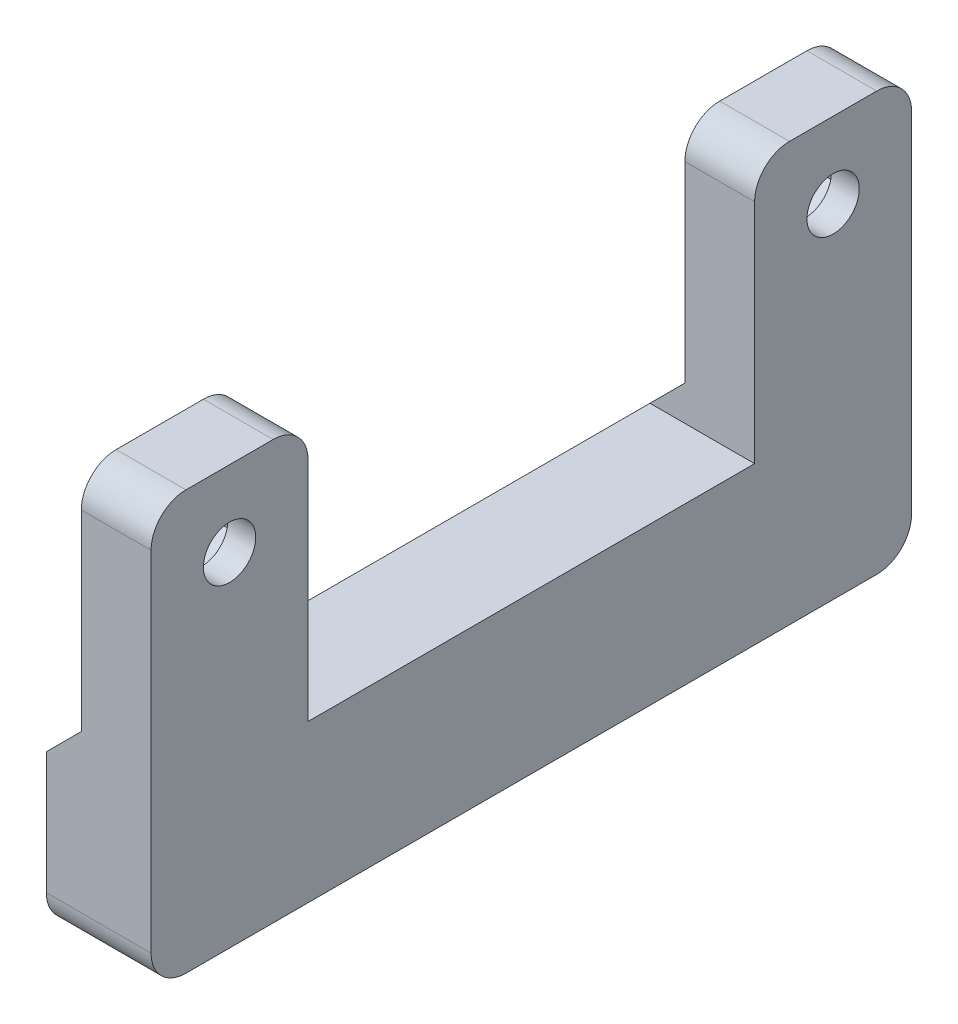
SolidWorks part; units mm, degrees
ref_plane "Спереди" through (0, 0, 0) normal (0, 0, 1) x (1, 0, 0)
ref_plane "Сверху" through (0, 0, 0) normal (0, 1, 0) x (1, 0, 0)
ref_plane "Справа" through (0, 0, 0) normal (1, 0, 0) x (0, 0, -1)
sketch "Эскиз1" plane through (0, 0, 0) normal (1, 0, 0) x (0, 0, -1)
  line L0 (-49.5833, 6.5417) -> (-49.5833, -17.4583)
  line L1 (-49.5833, -17.4583) -> (-5.9833, -17.4583)
  line L2 (-5.9833, -17.4583) -> (-5.9833, 6.5417)
  line L3 (-5.9833, 6.5417) -> (-14.9833, 6.5417)
  line L4 (-14.9833, 6.5417) -> (-14.9833, -8.4583)
  line L5 (-14.9833, -8.4583) -> (-40.5833, -8.4583)
  line L6 (-40.5833, -8.4583) -> (-40.5833, 6.5417)
  line L7 (-40.5833, 6.5417) -> (-49.5833, 6.5417)
  line L8 (-45.0833, 6.5417) -> (-45.0833, -17.4583) construction
  line L9 (-10.4833, 6.5417) -> (-10.4833, -17.4583) construction
  dimension "D1" = 24
  dimension "D2" = 9
  dimension "D3" = 9
  dimension "D4" = 9
  dimension "D5" = 15
  dimension "D6" = 34.6
  dimension "D7" = 24
extrude "Бобышка-Вытянуть1" add sketch "Эскиз1" along normal blind 4
sketch "Эскиз2" plane through (0, 0, 0) normal (-1, 0, 0) x (0, 0, 1)
  line L0 (10.4833, 6.5417) -> (10.4833, -17.4583) construction
  line L1 (5.9833, 6.5417) -> (14.9833, 6.5417) construction
  line L2 (49.5833, -17.4583) -> (5.9833, -17.4583) construction
  line L3 (45.0833, 6.5417) -> (45.0833, -17.4583) construction
  line L4 (40.5833, 6.5417) -> (49.5833, 6.5417) construction
  line L5 (5.9833, 2.191) -> (49.5833, 2.191) construction
  line L6 (5.9833, -17.4583) -> (5.9833, 6.5417) construction
  line L7 (49.5833, 6.5417) -> (49.5833, -17.4583) construction
  circle A0 centre (10.4833, 2.191) radius 1.5
  circle A1 centre (45.0833, 2.191) radius 1.5
extrude "Вырез-Вытянуть1" cut sketch "Эскиз2" against normal through all
sketch "Эскиз4" plane through (0, 0, 0) normal (-1, 0, 0) x (0, 0, 1)
  line L1 (10.4833, 5.3375) -> (7.7583, 3.7642)
  line L2 (7.7583, 3.7642) -> (7.7583, 0.6177)
  line L3 (7.7583, 0.6177) -> (10.4833, -0.9556)
  line L4 (10.4833, -0.9556) -> (13.2083, 0.6177)
  line L5 (13.2083, 0.6177) -> (13.2083, 3.7642)
  line L6 (13.2083, 3.7642) -> (10.4833, 5.3375)
  line L7 (45.0833, 5.3375) -> (42.3583, 3.7642)
  line L8 (42.3583, 3.7642) -> (42.3583, 0.6177)
  line L9 (42.3583, 0.6177) -> (45.0833, -0.9556)
  line L10 (45.0833, -0.9556) -> (47.8083, 0.6177)
  line L11 (47.8083, 0.6177) -> (47.8083, 3.7642)
  line L12 (47.8083, 3.7642) -> (45.0833, 5.3375)
  circle A0 centre (10.4833, 2.191) radius 2.725 construction
  circle A1 centre (45.0833, 2.191) radius 2.725 construction
extrude "Вырез-Вытянуть3" cut sketch "Эскиз4" against normal blind 2.4
sketch "Эскиз6" plane through (0, 0, 0) normal (-1, 0, 0) x (0, 0, 1)
  line L0 (5.9833, -6.4583) -> (14.9833, -6.4583)
  line L1 (5.9833, -17.4583) -> (5.9833, 6.5417) construction
  line L2 (14.9833, 6.5417) -> (14.9833, -8.4583) construction
  line L3 (14.9833, -6.4583) -> (14.9833, -8.4583)
  line L4 (14.9833, -8.4583) -> (40.5833, -8.4583)
  line L5 (40.5833, -8.4583) -> (40.5833, -6.4583)
  line L6 (40.5833, -8.4583) -> (40.5833, 6.5417) construction
  line L7 (40.5833, -6.4583) -> (49.5833, -6.4583)
  line L8 (49.5833, 6.5417) -> (49.5833, -17.4583) construction
  line L9 (49.5833, -6.4583) -> (49.5833, -17.4583)
  line L10 (49.5833, -17.4583) -> (5.9833, -17.4583)
  line L11 (49.5833, -17.4583) -> (5.9833, -17.4583) construction
  line L12 (5.9833, -17.4583) -> (5.9833, -6.4583)
  dimension "D1" = 11
  dimension "D2" = 11
extrude "Бобышка-Вытянуть2" add sketch "Эскиз6" along normal blind 2
fillet "Скругление3" radius 2 6 edges at (1, -17.4583, 49.5833) (2, 6.5417, 40.5833) (2, 6.5417, 49.5833) (2, 6.5417, 14.9833) (2, 6.5417, 5.9833) (1, -17.4583, 5.9833)
chamfer "Фаска1" distance 2 angle 45 2 edges at (-2, -6.4583, 10.4833) (-2, -6.4583, 45.0833)
